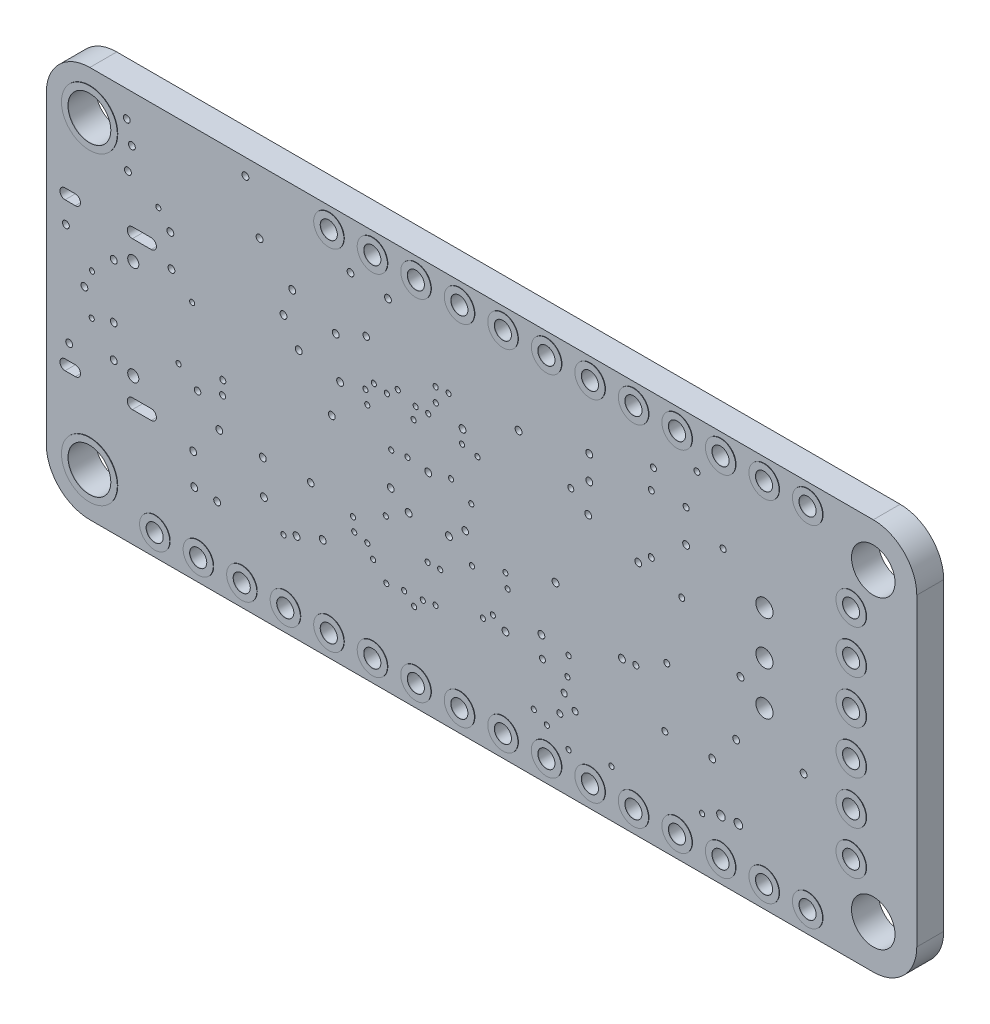
SolidWorks part; units mm, degrees
ref_plane "Front Plane" through (0, 0, 0) normal (0, 0, 1) x (1, 0, 0)
ref_plane "Top Plane" through (0, 0, 0) normal (0, 1, 0) x (1, 0, 0)
ref_plane "Right Plane" through (0, 0, 0) normal (1, 0, 0) x (0, 0, -1)
ref_plane "Plane1" through (0, 0, 0) normal (0, 0, -1) x (-1, 0, 0)
sketch "Sketch1" plane through (0, 0, 0) normal (0, 0, -1) x (-1, 0, 0)
  line L0 (-5.024, 6.81) -> (-6.124, 6.81)
  line L1 (-6.124, 7.41) -> (-5.024, 7.41)
  line L2 (-1.694, 16.05) -> (-1.094, 16.05)
  line L3 (-1.094, 15.45) -> (-1.694, 15.45)
  line L4 (-5.024, 15.45) -> (-6.124, 15.45)
  line L5 (-6.124, 16.05) -> (-5.024, 16.05)
  line L6 (-1.094, 6.81) -> (-1.694, 6.81)
  line L7 (-1.694, 7.41) -> (-1.094, 7.41)
  line L8 (0, 2.54) -> (0, 20.32)
  line L9 (-2.54, 22.86) -> (-48.26, 22.86)
  line L10 (-50.8, 20.32) -> (-50.8, 2.54)
  line L11 (-48.26, 0) -> (-2.54, 0)
  circle A0 centre (-48.26, 2.54) radius 1.27
  circle A1 centre (-48.26, 20.32) radius 1.27
  circle A2 centre (-41.91, 15.24) radius 0.5
  circle A3 centre (-41.91, 10.16) radius 0.5
  circle A4 centre (-46.99, 7.62) radius 0.5
  circle A5 centre (-46.99, 12.7) radius 0.5
  circle A6 centre (-46.99, 17.78) radius 0.5
  arc A7 (-6.124, 6.81) -> (-6.124, 7.41) centre (-6.124, 7.11) cw
  arc A8 (-5.024, 7.41) -> (-5.024, 6.81) centre (-5.024, 7.11) cw
  arc A9 (-1.094, 16.05) -> (-1.094, 15.45) centre (-1.094, 15.75) cw
  arc A10 (-1.694, 15.45) -> (-1.694, 16.05) centre (-1.694, 15.75) cw
  circle A11 centre (-5.074, 8.54) radius 0.325
  circle A12 centre (-41.91, 21.654) radius 0.5
  circle A13 centre (-36.83, 21.654) radius 0.5
  circle A14 centre (-31.75, 21.654) radius 0.5
  circle A15 centre (-26.67, 21.654) radius 0.5
  circle A16 centre (-21.59, 21.654) radius 0.5
  circle A17 centre (-16.51, 21.654) radius 0.5
  circle A18 centre (-8.89, 1.27) radius 0.5
  circle A19 centre (-13.97, 1.27) radius 0.5
  circle A20 centre (-19.05, 1.27) radius 0.5
  circle A21 centre (-24.13, 1.27) radius 0.5
  circle A22 centre (-29.21, 1.27) radius 0.5
  circle A23 centre (-34.29, 1.27) radius 0.5
  circle A24 centre (-39.37, 1.27) radius 0.5
  circle A25 centre (-44.45, 1.27) radius 0.5
  circle A26 centre (-2.54, 20.32) radius 1.25
  circle A27 centre (-37.084, 13.335) radius 0.175
  circle A28 centre (-30.416, 5.997) radius 0.15
  circle A29 centre (-30.861, 4.488) radius 0.175
  circle A30 centre (-29.969, 3.92) radius 0.175
  circle A31 centre (-36.101, 6.087) radius 0.175
  circle A32 centre (-17.97, 7.099) radius 0.15
  circle A33 centre (-18.732, 6.922) radius 0.15
  circle A34 centre (-17.9, 7.831) radius 0.15
  circle A35 centre (-21.971, 5.652) radius 0.15
  circle A36 centre (-39.497, 17.018) radius 0.175
  circle A37 centre (-30.223, 5.083) radius 0.175
  circle A38 centre (-13.843, 4.89) radius 0.15
  circle A39 centre (-2.667, 12.636) radius 0.15
  circle A40 centre (-26.06, 6.947) radius 0.15
  circle A41 centre (-24.259, 14.685) radius 0.15
  circle A42 centre (-24.846, 8.826) radius 0.15
  circle A43 centre (-28.956, 6.167) radius 0.175
  circle A44 centre (-32.984, 2.766) radius 0.15
  circle A45 centre (-23.622, 12.609) radius 0.15
  circle A46 centre (-22.72, 5.766) radius 0.15
  circle A47 centre (-4.699, 21.336) radius 0.197
  circle A48 centre (-26.924, 8.694) radius 0.15
  circle A49 centre (-26.792, 9.452) radius 0.15
  circle A50 centre (-22.728, 16.002) radius 0.15
  circle A51 centre (-20.51, 15.558) radius 0.15
  circle A52 centre (-23.479, 16.86) radius 0.15
  circle A53 centre (-37.338, 18.034) radius 0.175
  circle A54 centre (-22.722, 16.814) radius 0.15
  circle A55 centre (-18.732, 13.906) radius 0.15
  circle A56 centre (-18.669, 17.336) radius 0.1905
  circle A57 centre (-4.762, 18.732) radius 0.2
  circle A58 centre (-3.937, 8.763) radius 0.2
  circle A59 centre (-35.306, 14.478) radius 0.175
  circle A60 centre (-24.29, 15.466) radius 0.2
  circle A61 centre (-15.43, 8.318) radius 0.1905
  circle A62 centre (-16.662, 12.333) radius 0.197
  circle A63 centre (-19.114, 15.176) radius 0.15
  circle A64 centre (-22.255, 7.711) radius 0.15
  circle A65 centre (-21.553, 15.233) radius 0.15
  circle A66 centre (-44.196, 8.001) radius 0.2
  circle A67 centre (-40.513, 11.049) radius 0.2
  circle A68 centre (-26.797, 6.477) radius 0.2
  circle A69 centre (-37.338, 16.129) radius 0.2
  circle A70 centre (-38.862, 6.096) radius 0.2
  circle A71 centre (-31.686, 17.907) radius 0.2
  circle A72 centre (-31.623, 14.796) radius 0.2
  circle A73 centre (-12.446, 19.177) radius 0.2
  circle A74 centre (-7.302, 15.05) radius 0.2
  circle A75 centre (-1.143, 14.224) radius 0.2
  circle A76 centre (-2.222, 11.62) radius 0.2
  circle A77 centre (-14.605, 5.207) radius 0.2
  circle A78 centre (-14.732, 14.668) radius 0.2
  circle A79 centre (-12.636, 8.192) radius 0.2
  circle A80 centre (-16.891, 16.574) radius 0.2
  circle A81 centre (-28.892, 7.366) radius 0.2
  circle A82 centre (-23.495, 9.652) radius 0.2
  circle A83 centre (-12.7, 6.223) radius 0.2
  circle A84 centre (-8.572, 6.477) radius 0.2
  circle A85 centre (-4.995, 20.13) radius 0.2
  circle A86 centre (-10.096, 8.318) radius 0.2
  circle A87 centre (-9.97, 4.636) radius 0.2
  circle A88 centre (-16.129, 5.778) radius 0.2
  circle A89 centre (-21.146, 9.652) radius 0.2
  circle A90 centre (-13.843, 16.002) radius 0.2
  circle A91 centre (-27.559, 17.018) radius 0.2
  circle A92 centre (-17.145, 14.262) radius 0.2
  circle A93 centre (-8.636, 4.699) radius 0.2
  circle A94 centre (-22.288, 12.268) radius 0.2
  circle A95 centre (-1.334, 8.318) radius 0.2
  circle A96 centre (-7.239, 16.891) radius 0.2
  circle A97 centre (-19.939, 19.876) radius 0.2
  circle A98 centre (-14.351, 17.526) radius 0.2
  circle A99 centre (-31.686, 16.51) radius 0.2
  circle A100 centre (-29.718, 10.414) radius 0.2
  circle A101 centre (-40.386, 3.556) radius 0.25
  circle A102 centre (-33.592, 8.509) radius 0.2
  circle A103 centre (-34.544, 13.843) radius 0.2
  circle A104 centre (-40.259, 7.747) radius 0.2
  circle A105 centre (-20.13, 12.319) radius 0.15
  circle A106 centre (-21.077, 12.429) radius 0.15
  circle A107 centre (-25.477, 6.496) radius 0.15
  circle A108 centre (-18.624, 14.631) radius 0.15
  circle A109 centre (-20.098, 10.382) radius 0.197
  circle A110 centre (-24.447, 10.401) radius 0.1905
  circle A111 centre (-30.607, 15.629) radius 0.175
  circle A112 centre (-3.937, 13.843) radius 0.2
  circle A113 centre (-3.937, 10.668) radius 0.2
  circle A114 centre (-8.826, 9.652) radius 0.1905
  circle A115 centre (-10.302, 10.942) radius 0.175
  circle A116 centre (-6.54, 17.78) radius 0.15
  circle A117 centre (-35.306, 17.872) radius 0.175
  circle A118 centre (-37.973, 20.152) radius 0.175
  circle A119 centre (-35.433, 19.075) radius 0.175
  circle A120 centre (-22.288, 15.24) radius 0.15
  circle A121 centre (-19.876, 15.05) radius 0.15
  circle A122 centre (-7.722, 10.478) radius 0.15
  circle A123 centre (-8.509, 13.97) radius 0.15
  circle A124 centre (-17.753, 20.093) radius 0.197
  circle A125 centre (-24.801, 11.938) radius 0.15
  circle A126 centre (-11.62, 21.908) radius 0.2
  circle A127 centre (-38.269, 3.02) radius 0.15
  circle A128 centre (-19.812, 8.826) radius 0.15
  circle A129 centre (-25.163, 14.502) radius 0.15
  circle A130 centre (-22.987, 7.711) radius 0.15
  circle A131 centre (-2.65, 10.24) radius 0.15
  circle A132 centre (-21.432, 14.506) radius 0.15
  circle A133 centre (-20.884, 5.588) radius 0.15
  circle A134 centre (-36.21, 9.588) radius 0.175
  circle A135 centre (-39.37, 3.463) radius 0.25
  circle A136 centre (-30.48, 7.112) radius 0.15
  circle A137 centre (-30.48, 2.35) radius 0.15
  circle A138 centre (-28.448, 3.373) radius 0.15
  circle A139 centre (-29.21, 2.957) radius 0.15
  circle A140 centre (-19.071, 6.262) radius 0.15
  circle A141 centre (-19.842, 5.434) radius 0.15
  circle A142 centre (-21.463, 5.08) radius 0.15
  circle A143 centre (-34.406, 8.583) radius 0.175
  circle A144 centre (-10.287, 10.16) radius 0.175
  circle A145 centre (-2.54, 2.54) radius 1.25
  circle A146 centre (-41.91, 1.27) radius 0.5
  circle A147 centre (-36.83, 1.27) radius 0.5
  circle A148 centre (-31.75, 1.27) radius 0.5
  circle A149 centre (-26.67, 1.27) radius 0.5
  circle A150 centre (-21.59, 1.27) radius 0.5
  circle A151 centre (-16.51, 1.27) radius 0.5
  circle A152 centre (-11.43, 1.27) radius 0.5
  circle A153 centre (-6.35, 1.27) radius 0.5
  circle A154 centre (-19.05, 21.654) radius 0.5
  circle A155 centre (-24.13, 21.654) radius 0.5
  circle A156 centre (-29.21, 21.654) radius 0.5
  circle A157 centre (-34.29, 21.654) radius 0.5
  circle A158 centre (-39.37, 21.654) radius 0.5
  circle A159 centre (-44.45, 21.654) radius 0.5
  circle A160 centre (-5.074, 14.32) radius 0.325
  arc A161 (-6.124, 15.45) -> (-6.124, 16.05) centre (-6.124, 15.75) cw
  arc A162 (-5.024, 16.05) -> (-5.024, 15.45) centre (-5.024, 15.75) cw
  arc A163 (-1.694, 6.81) -> (-1.694, 7.41) centre (-1.694, 7.11) cw
  arc A164 (-1.094, 7.41) -> (-1.094, 6.81) centre (-1.094, 7.11) cw
  circle A165 centre (-46.99, 15.24) radius 0.5
  circle A166 centre (-46.99, 10.16) radius 0.5
  circle A167 centre (-46.99, 5.08) radius 0.5
  circle A168 centre (-41.91, 12.7) radius 0.5
  arc A169 (-2.54, 0) -> (0, 2.54) centre (-2.54, 2.54) ccw
  arc A170 (0, 20.32) -> (-2.54, 22.86) centre (-2.54, 20.32) ccw
  arc A171 (-48.26, 22.86) -> (-50.8, 20.32) centre (-48.26, 20.32) ccw
  arc A172 (-50.8, 2.54) -> (-48.26, 0) centre (-48.26, 2.54) ccw
extrude "Boss-Extrude1" add sketch "Sketch1" against normal blind 1.57
sketch "Sketch2" plane through (0, 0, 1.57) normal (0, 0, 1) x (1, 0, 0)
  circle A0 centre (46.99, 5.08) radius 0.5 construction
  circle A1 centre (46.99, 7.62) radius 0.5 construction
  circle A2 centre (46.99, 10.16) radius 0.5 construction
  circle A3 centre (46.99, 12.7) radius 0.5 construction
  circle A4 centre (46.99, 15.24) radius 0.5 construction
  circle A5 centre (46.99, 17.78) radius 0.5 construction
  circle A6 centre (44.45, 1.27) radius 0.5 construction
  circle A7 centre (41.91, 1.27) radius 0.5 construction
  circle A8 centre (39.37, 1.27) radius 0.5 construction
  circle A9 centre (36.83, 1.27) radius 0.5 construction
  circle A10 centre (34.29, 1.27) radius 0.5 construction
  circle A11 centre (31.75, 1.27) radius 0.5 construction
  circle A12 centre (29.21, 1.27) radius 0.5 construction
  circle A13 centre (26.67, 1.27) radius 0.5 construction
  circle A14 centre (24.13, 1.27) radius 0.5 construction
  circle A15 centre (21.59, 1.27) radius 0.5 construction
  circle A16 centre (19.05, 1.27) radius 0.5 construction
  circle A17 centre (16.51, 1.27) radius 0.5 construction
  circle A18 centre (13.97, 1.27) radius 0.5 construction
  circle A19 centre (11.43, 1.27) radius 0.5 construction
  circle A20 centre (8.89, 1.27) radius 0.5 construction
  circle A21 centre (6.35, 1.27) radius 0.5 construction
  circle A22 centre (44.45, 21.654) radius 0.5 construction
  circle A23 centre (41.91, 21.654) radius 0.5 construction
  circle A24 centre (39.37, 21.654) radius 0.5 construction
  circle A25 centre (36.83, 21.654) radius 0.5 construction
  circle A26 centre (34.29, 21.654) radius 0.5 construction
  circle A27 centre (31.75, 21.654) radius 0.5 construction
  circle A28 centre (29.21, 21.654) radius 0.5 construction
  circle A29 centre (26.67, 21.654) radius 0.5 construction
  circle A30 centre (24.13, 21.654) radius 0.5 construction
  circle A31 centre (21.59, 21.654) radius 0.5 construction
  circle A32 centre (19.05, 21.654) radius 0.5 construction
  circle A33 centre (16.51, 21.654) radius 0.5 construction
  circle A34 centre (2.54, 2.54) radius 1.25 construction
  circle A35 centre (2.54, 20.32) radius 1.25 construction
  circle A36 centre (46.99, 5.08) radius 0.5
  circle A37 centre (46.99, 7.62) radius 0.5
  circle A38 centre (46.99, 10.16) radius 0.5
  circle A39 centre (46.99, 12.7) radius 0.5
  circle A40 centre (46.99, 15.24) radius 0.5
  circle A41 centre (46.99, 17.78) radius 0.5
  circle A42 centre (44.45, 1.27) radius 0.5
  circle A43 centre (41.91, 1.27) radius 0.5
  circle A44 centre (39.37, 1.27) radius 0.5
  circle A45 centre (36.83, 1.27) radius 0.5
  circle A46 centre (34.29, 1.27) radius 0.5
  circle A47 centre (31.75, 1.27) radius 0.5
  circle A48 centre (29.21, 1.27) radius 0.5
  circle A49 centre (26.67, 1.27) radius 0.5
  circle A50 centre (24.13, 1.27) radius 0.5
  circle A51 centre (21.59, 1.27) radius 0.5
  circle A52 centre (19.05, 1.27) radius 0.5
  circle A53 centre (16.51, 1.27) radius 0.5
  circle A54 centre (13.97, 1.27) radius 0.5
  circle A55 centre (11.43, 1.27) radius 0.5
  circle A56 centre (8.89, 1.27) radius 0.5
  circle A57 centre (6.35, 1.27) radius 0.5
  circle A58 centre (44.45, 21.654) radius 0.5
  circle A59 centre (41.91, 21.654) radius 0.5
  circle A60 centre (39.37, 21.654) radius 0.5
  circle A61 centre (36.83, 21.654) radius 0.5
  circle A62 centre (34.29, 21.654) radius 0.5
  circle A63 centre (31.75, 21.654) radius 0.5
  circle A64 centre (29.21, 21.654) radius 0.5
  circle A65 centre (26.67, 21.654) radius 0.5
  circle A66 centre (24.13, 21.654) radius 0.5
  circle A67 centre (21.59, 21.654) radius 0.5
  circle A68 centre (19.05, 21.654) radius 0.5
  circle A69 centre (16.51, 21.654) radius 0.5
  circle A70 centre (2.54, 2.54) radius 1.25
  circle A71 centre (2.54, 20.32) radius 1.25
  circle A72 centre (46.99, 5.08) radius 0.881
  circle A73 centre (46.99, 7.62) radius 0.881
  circle A74 centre (46.99, 10.16) radius 0.881
  circle A75 centre (46.99, 12.7) radius 0.881
  circle A76 centre (46.99, 15.24) radius 0.881
  circle A77 centre (46.99, 17.78) radius 0.881
  circle A78 centre (44.45, 1.27) radius 0.881
  circle A79 centre (41.91, 1.27) radius 0.881
  circle A80 centre (39.37, 1.27) radius 0.881
  circle A81 centre (36.83, 1.27) radius 0.881
  circle A82 centre (34.29, 1.27) radius 0.881
  circle A83 centre (31.75, 1.27) radius 0.881
  circle A84 centre (29.21, 1.27) radius 0.881
  circle A85 centre (26.67, 1.27) radius 0.881
  circle A86 centre (24.13, 1.27) radius 0.881
  circle A87 centre (21.59, 1.27) radius 0.881
  circle A88 centre (19.05, 1.27) radius 0.881
  circle A89 centre (16.51, 1.27) radius 0.881
  circle A90 centre (13.97, 1.27) radius 0.881
  circle A91 centre (11.43, 1.27) radius 0.881
  circle A92 centre (8.89, 1.27) radius 0.881
  circle A93 centre (6.35, 1.27) radius 0.881
  circle A94 centre (44.45, 21.654) radius 0.881
  circle A95 centre (41.91, 21.654) radius 0.881
  circle A96 centre (39.37, 21.654) radius 0.881
  circle A97 centre (36.83, 21.654) radius 0.881
  circle A98 centre (34.29, 21.654) radius 0.881
  circle A99 centre (31.75, 21.654) radius 0.881
  circle A100 centre (29.21, 21.654) radius 0.881
  circle A101 centre (26.67, 21.654) radius 0.881
  circle A102 centre (24.13, 21.654) radius 0.881
  circle A103 centre (21.59, 21.654) radius 0.881
  circle A104 centre (19.05, 21.654) radius 0.881
  circle A105 centre (16.51, 21.654) radius 0.881
  circle A106 centre (2.54, 2.54) radius 1.631
  circle A107 centre (2.54, 20.32) radius 1.631
  dimension "D1" = 0.381
extrude "Boss-Extrude2" add sketch "Sketch2" along normal blind 0.0254 separate body
ref_plane "Plane2" through (0, 0, 0.785) normal (0, 0, -1) x (-1, 0, 0)
mirror "Mirror1" about plane through (0, 0, 0.785) normal (0, 0, -1) of "Boss-Extrude2"
